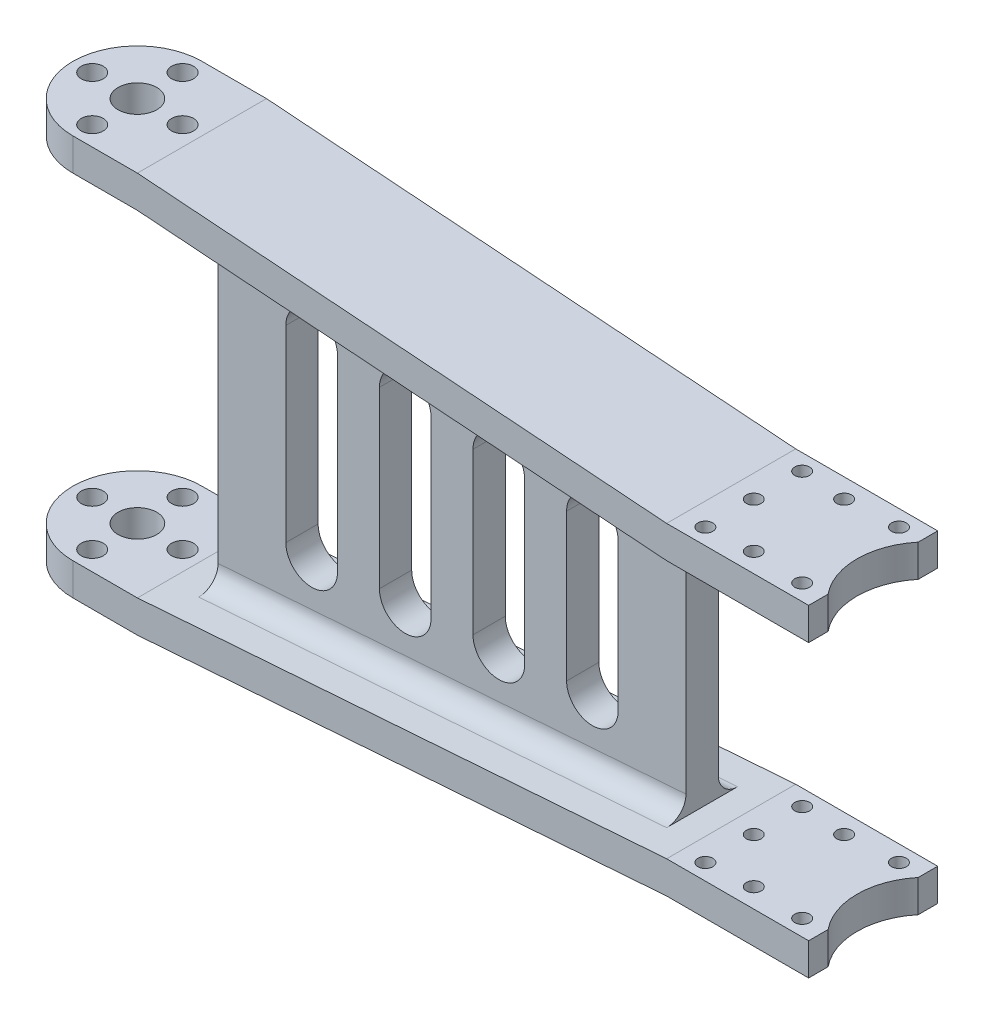
SolidWorks part; units mm, degrees
ref_plane "前视基准面" through (0, 0, 0) normal (0, 0, 1) x (1, 0, 0)
ref_plane "上视基准面" through (0, 0, 0) normal (0, 1, 0) x (1, 0, 0)
ref_plane "右视基准面" through (0, 0, 0) normal (1, 0, 0) x (0, 0, -1)
sketch "草图1" plane through (0, 0, 0) normal (0, 1, 0) x (1, 0, 0)
  line L0 (0, 0) -> (102.5, 0) construction
  line L1 (102.5, 0) -> (122.5, 0) construction
  line L2 (0, 10) -> (114, 10)
  line L3 (114, 10) -> (114, -10)
  line L4 (114, -10) -> (0, -10)
  line L5 (92, 10) -> (92, -10) construction
  line L7 (95.5, -7.5) -> (110.5, -7.5) construction
  line L8 (95.5, -7.5) -> (95.5, 7.5) construction
  line L9 (95.5, 7.5) -> (110.5, 7.5) construction
  line L10 (110.5, -7.5) -> (110.5, 7.5) construction
  line L11 (95.5, -7.5) -> (110.5, 7.5) construction
  line L12 (95.5, 7.5) -> (110.5, -7.5) construction
  circle A0 centre (0, 0) radius 10
  circle A1 centre (0, 0) radius 7 construction
  circle A2 centre (0, 7) radius 1.7
  circle A3 centre (7, 0) radius 1.7
  circle A4 centre (0, -7) radius 1.7
  circle A5 centre (-7, 0) radius 1.7
  circle A6 centre (0, 0) radius 3
  circle A7 centre (102.5, 0) radius 7 construction
  circle A8 centre (102.5, 7) radius 1.15
  circle A9 centre (95.5, 0) radius 1.15
  circle A10 centre (102.5, -7) radius 1.15
  circle A11 centre (95.5, 7.5) radius 1.15
  circle A12 centre (95.5, -7.5) radius 1.15
  circle A13 centre (110.5, -7.5) radius 1.15
  circle A14 centre (110.5, 7.5) radius 1.15
  circle A15 centre (122.5, 0) radius 11
  point P21 (0, 0)
  point P29 (103, 0)
  dimension "D3" = 20
  dimension "D4" = 3.4
  dimension "D6" = 14
  dimension "D7" = 6
  dimension "D12" = 2.3
  dimension "D13" = 22
  dimension "D1" = 122.5
  dimension "D2" = 20
  dimension "D8" = 10.5
  dimension "D9" = 3.5
  dimension "D10" = 15
  dimension "D11" = 3.5
  dimension "D5" = 4
extrude "凸台-拉伸1" add sketch "草图1" along normal blind 11 contours A0 A6 A5 A4 A3 A2 | A15 L3 L2 A0 L4 A14 A13 A12 A11 A10 A9 A8 region at (59.7287, 0, 0) region at (6.8711, 0, -6.8711)
extrude "凸台-拉伸2" add sketch "草图1<3>" along normal blind 11 from offset 51 separate body contours A15 L3 L2 A0 L4 A14 A13 A12 A11 A10 A9 A8 | A0 A6 A5 A4 A3 A2 region at (59.7287, 0, 0) region at (6.8711, 0, -6.8711)
sketch "草图1<3>" plane through (0, 0, 0) normal (0, 1, 0) x (1, 0, 0) same geometry as "草图1"
sketch "草图4" plane through (0, 0, 10) normal (0, 0, 1) x (1, 0, 0)
  line L0 (0, 0) -> (0, 62) construction
  line L1 (-10, 5) -> (10, 5)
  line L2 (-10, 5) -> (-10, 57)
  line L3 (-10, 57) -> (10, 57)
  line L4 (10, 5) -> (10, 57)
  line L5 (114, 62) -> (111.5, 62) construction
  line L6 (114, 11) -> (0, 11) construction
  line L7 (114, 51) -> (92, 51)
  line L8 (114, 51) -> (114, 11)
  line L9 (114, 11) -> (92, 11)
  line L10 (92, 51) -> (92, 11)
  line L11 (10, 57) -> (92, 51)
  line L12 (10, 5) -> (92, 11)
  line L18 (0, 11) -> (-10, 11) construction
  line L24 (10, 62) -> (92, 56)
  line L25 (114, 62) -> (0, 62) construction
  line L26 (92, 56) -> (114, 56)
  line L28 (114, 56) -> (114, 62)
  line L29 (114, 62) -> (10, 62)
  line L30 (10, 0) -> (114, 0)
  line L31 (114, 0) -> (0, 0) construction
  line L32 (114, 0) -> (114, 6)
  line L33 (114, 11) -> (114, 0) construction
  line L34 (114, 6) -> (92, 6)
  line L35 (92, 6) -> (10, 0)
  line L36 (114, 62) -> (114, 51) construction
  line L37 (92, 6) -> (92, 11) construction
  line L38 (10, 57) -> (10, 62) construction
  line L39 (10, 5) -> (10, 0) construction
  line L41 (92, 56) -> (92, 51) construction
  point P10 (0, 5)
  line M4 (0, 51) -> (114, 51)
  line M5 (114, 51) -> (114, 62)
  line M6 (114, 62) -> (0, 62)
  line M7 (0, 62) -> (0, 51)
  dimension "D1" = 52
  dimension "D2" = 20
  dimension "D3" = 6
  dimension "D4" = 22
  dimension "D5" = 5
extrude "切除-拉伸1" cut sketch "草图4" against normal through all contours L0 L1 L4 M4 | L4 L3 M4 M7 | L1 L0 L3 L2 M7 | L10 L9 L8 M4 | L4 L12 L10 M4 | L11 L4 M4 | L34 L35 L30 L32 | L24 L26 M5 M6 region at (-0.3061, 29.5918, 10) region at (50.0465, 29.4651, 10) region at (5, 54, 10) region at (37.3333, 53, 10) region at (103, 31, 10) region at (78.0529, 59.6508, 10) region at (78.0529, 2.3492, 10)
sketch "草图5" plane through (0, 0, 0) normal (0, 0, 1) x (1, 0, 0)
  line L0 (15, 56.6341) -> (15, 5.3659)
  line L1 (15, 5.3659) -> (87.5, 10.6707)
  line L2 (87.5, 10.6707) -> (87.5, 51.3293)
  line L3 (87.5, 51.3293) -> (15, 56.6341)
  line L4 (10, 57) -> (92, 51) construction
  line L5 (10, 5) -> (92, 11) construction
  dimension "D1" = 15
  dimension "D2" = 72.5
extrude "凸台-拉伸4" add sketch "草图5" against normal blind 2.5 and the other way blind 2.5
sketch "草图9" plane through (0, 0, 2.5) normal (0, 0, 1) x (1, 0, 0)
  line L0 (15, 31) -> (29.5, 31) construction
  line L2 (15, 56.6341) -> (15, 5.3659) construction
  line L3 (29.5, 31) -> (44, 31) construction
  line L5 (44, 31) -> (58.5, 31) construction
  line L6 (58.5, 31) -> (73, 31) construction
  line L7 (73, 31) -> (87.5, 31) construction
  line L8 (87.5, 10.6707) -> (87.5, 51.3293) construction
  line L9 (29.5, 45.5732) -> (29.5, 16.4268) construction
  line L10 (33.5, 45.5732) -> (33.5, 16.4268)
  line L11 (25.5, 45.5732) -> (25.5, 16.4268)
  line L12 (44, 44.5122) -> (44, 17.4878) construction
  line L13 (48, 44.5122) -> (48, 17.4878)
  line L14 (40, 44.5122) -> (40, 17.4878)
  line L15 (58.5, 43.4512) -> (58.5, 18.5488) construction
  line L16 (62.5, 43.4512) -> (62.5, 18.5488)
  line L17 (54.5, 43.4512) -> (54.5, 18.5488)
  line L18 (73, 42.3902) -> (73, 19.6098) construction
  line L19 (77, 42.3902) -> (77, 19.6098)
  line L20 (69, 42.3902) -> (69, 19.6098)
  line L21 (25.5, 45.5732) -> (33.5, 45.5732) construction
  line L22 (40, 44.5122) -> (48, 44.5122) construction
  line L23 (54.5, 43.4512) -> (62.5, 43.4512) construction
  line L24 (69, 42.3902) -> (77, 42.3902) construction
  line L25 (29.5, 45.5732) -> (29.5, 55.5732) construction
  line L26 (10, 57) -> (92, 51) construction
  line L27 (44, 44.5122) -> (44, 54.5122) construction
  line L28 (87.5, 51.3293) -> (15, 56.6341) construction
  line L29 (58.5, 43.4512) -> (58.5, 53.4512) construction
  line L30 (73, 42.3902) -> (73, 52.3902) construction
  arc A0 (33.5, 45.5732) -> (25.5, 45.5732) centre (29.5, 45.5732) ccw
  arc A1 (25.5, 16.4268) -> (33.5, 16.4268) centre (29.5, 16.4268) ccw
  arc A2 (48, 44.5122) -> (40, 44.5122) centre (44, 44.5122) ccw
  arc A3 (40, 17.4878) -> (48, 17.4878) centre (44, 17.4878) ccw
  arc A4 (62.5, 43.4512) -> (54.5, 43.4512) centre (58.5, 43.4512) ccw
  arc A5 (54.5, 18.5488) -> (62.5, 18.5488) centre (58.5, 18.5488) ccw
  arc A6 (77, 42.3902) -> (69, 42.3902) centre (73, 42.3902) ccw
  arc A7 (69, 19.6098) -> (77, 19.6098) centre (73, 19.6098) ccw
  point P12 (29.5, 31)
  point P17 (44, 31)
  point P24 (58.5, 31)
  point P31 (73, 31)
  dimension "D1" = 8
  dimension "D2" = 10
extrude "切除-拉伸2" cut sketch "草图9" against normal through all
fillet "圆角1" radius 3 4 edges at (51.25, 8.0183, -2.5) (51.25, 53.9817, -2.5) (51.25, 53.9817, 2.5) (51.25, 8.0183, 2.5)
